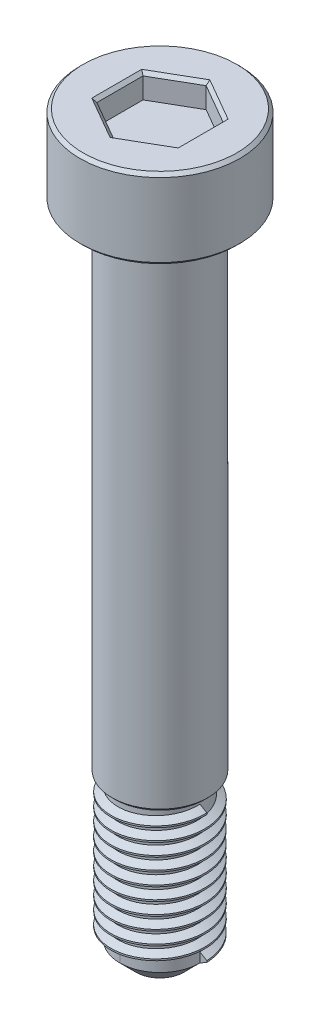
SolidWorks part; units mm, degrees
ref_plane "Front Plane" through (0, 0, 0) normal (0, 0, 1) x (1, 0, 0)
ref_plane "Top Plane" through (0, 0, 0) normal (0, 1, 0) x (1, 0, 0)
ref_plane "Right Plane" through (0, 0, 0) normal (1, 0, 0) x (0, 0, -1)
sketch "Sketch1" plane through (0, 0, 0) normal (0, 0, 1) x (1, 0, 0)
  line L0 (0, 92.3708) -> (0, 0) construction
  line L1 (0, 46) -> (5, 46)
  line L2 (5, 46) -> (5, 41)
  line L3 (5, 41) -> (2, 41)
  line L4 (2, 41) -> (2, 40)
  line L5 (2, 40) -> (3, 40)
  line L6 (3, 40) -> (3, 10)
  line L7 (2.5, 10) -> (3, 10)
  line L8 (2.5, 10) -> (2.5, 0)
  line L9 (2.5, 0) -> (0, 0)
  line L10 (0, 0) -> (0, 46)
  dimension "D1" = 30
  dimension "D2" = 10
  dimension "D3" = 6
  dimension "D4" = 5
  dimension "D5" = 10
  dimension "D6" = 5
  dimension "D7" = 1
  dimension "D8" = 4
revolve "Revolve1" add sketch "Sketch1" angle 360 about L0
sketch "Sketch2" plane through (0, 46, 0) normal (0, 1, 0) x (1, 0, 0)
  line L1 (0, 2.8868) -> (-2.5, 1.4434)
  line L2 (-2.5, 1.4434) -> (-2.5, -1.4434)
  line L3 (-2.5, -1.4434) -> (0, -2.8868)
  line L4 (0, -2.8868) -> (2.5, -1.4434)
  line L5 (2.5, -1.4434) -> (2.5, 1.4434)
  line L6 (2.5, 1.4434) -> (0, 2.8868)
  circle A0 centre (0, 0) radius 2.5 construction
  dimension "D1" = 5
extrude "Cut-Extrude1" cut sketch "Sketch2" against normal blind 1.5
chamfer "Chamfer1" distance 0.2 angle 45 7 edges at (0, 46, 5) (-2.5, 46, 0) (-1.25, 46, 2.1651) (1.25, 46, 2.1651) (2.5, 46, 0) (1.25, 46, -2.1651) (-1.25, 46, -2.1651)
chamfer "Chamfer2" distance 0.2 angle 45 2 edges at (0, 41, 2) (0, 41, 5)
chamfer "Chamfer3" distance 0.2 angle 45 2 edges at (0, 40, 3) (0, 40, 2)
chamfer "Chamfer4" distance 0.2 angle 45 2 edges at (0, 10, 2.5) (0, 10, 3)
chamfer "Chamfer5" distance 1 angle 45 1 edges at (0, 0, 2.5)
thread "Thread1" pitch 0.8 method extrude profile "Thread Profile1" start angle 0, offset 0, length 8, pitch 0.8, diameter 5
ref_plane "Plane1" through (2.5, 1, 0) normal (0, 0, 1) x (1, 0, 0)
sketch "Thread Profile1" plane through (2.5, 1, 0) normal (0, 0, 1) x (1, 0, 0)
  line L0 (0, 0) -> (0, 0.8) construction
  line L1 (0, 0) -> (0.433, 0.25)
  line L2 (0.433, 0.25) -> (0.433, 0.35)
  line L3 (0.433, 0.35) -> (0, 0.6)
  line L4 (0.433, 0.3) -> (0, 0.3) construction
  line L11 (0, 0) -> (0, 0.6)
  point P2 (0, 0)
  dimension "Pitch" = 0.8
  dimension "Profile_Angle" = 60
  dimension "Profile_Land" = 0.1
  dimension "Profile_Height" = 0.433
